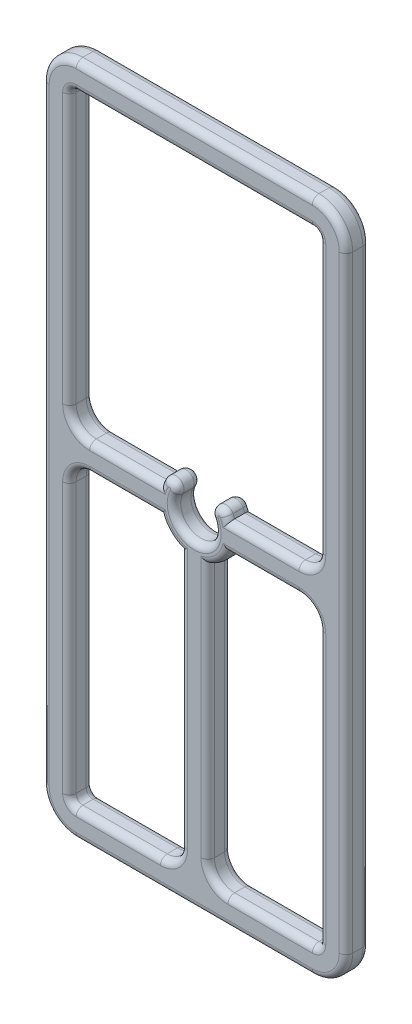
SolidWorks part; units mm, degrees
ref_plane "Front" through (0, 0, 0) normal (0, 0, 1) x (1, 0, 0)
ref_plane "Top" through (0, 0, 0) normal (0, 1, 0) x (1, 0, 0)
ref_plane "Right" through (0, 0, 0) normal (1, 0, 0) x (0, 0, -1)
sketch "Sketch1" plane through (0, 0, 0) normal (0, 0, 1) x (1, 0, 0)
  line L0 (0, -50) -> (0, 50) construction
  line L1 (-18.5, -46) -> (-18.5, -2)
  line L2 (18.5, 46) -> (-18.5, 46)
  line L3 (18.5, -46) -> (18.5, -2)
  line L4 (18.5, -46) -> (2, -46)
  line L5 (-2, -5.016) -> (-2, -46)
  line L6 (2, -5.016) -> (2, -46)
  line L7 (-2, -46) -> (-18.5, -46)
  line L8 (18.5, -46) -> (-18.5, -46) construction
  line L9 (22.5, -50) -> (-22.5, -50)
  line L10 (22.5, -50) -> (22.5, 50)
  line L11 (22.5, 50) -> (-22.5, 50)
  line L12 (-22.5, -50) -> (-22.5, 50)
  line L13 (22.5, -50) -> (-22.5, 50) construction
  line L14 (22.5, 50) -> (-22.5, -50) construction
  line L15 (0, 0) -> (-22.5, 0) construction
  line L16 (-18.5, 2) -> (-5.016, 2)
  line L17 (-18.5, -2) -> (-5.016, -2)
  line L18 (18.5, -2) -> (5.016, -2)
  line L19 (18.5, 2) -> (5.016, 2)
  line L20 (-18.5, 2) -> (-18.5, 46)
  line L21 (-18.5, -46) -> (-18.5, 46) construction
  line L22 (18.5, 2) -> (18.5, 46)
  line L23 (18.5, -46) -> (18.5, 46) construction
  arc A0 (-2.6429, 1.4196) -> (2.6429, 1.4196) centre (0, 0) ccw
  arc A1 (-5.016, -2) -> (-2, -5.016) centre (0, 0) ccw
  arc A2 (-4.7571, 2.5553) -> (-2.6429, 1.4196) centre (-3.7, 1.9875) cw
  arc A3 (4.7571, 2.5553) -> (2.6429, 1.4196) centre (3.7, 1.9875) ccw
  arc A4 (-4.7571, 2.5553) -> (-5.016, 2) centre (0, 0) ccw
  arc A5 (2, -5.016) -> (5.016, -2) centre (0, 0) ccw
  arc A6 (5.016, 2) -> (4.7571, 2.5553) centre (0, 0) ccw
  point P24 (0, 0)
  point P27 (0, 0)
  dimension "D1" = 6
  dimension "D2" = 2.4
  dimension "D3" = 5
  dimension "D4" = 100
  dimension "D5" = 45
  dimension "D7" = 4
  dimension "D8" = 4
  dimension "D6" = 4
extrude "Boss-Extrude2" add sketch "Sketch1" along normal blind 3.5
fillet "Fillet2" radius 5 4 edges at (-22.5, 50, 1.75) (-22.5, -50, 1.75) (22.5, -50, 1.75) (22.5, 50, 1.75)
fillet "Fillet3" radius 1 4 edges at (-18.5, 46, 1.75) (18.5, 46, 1.75) (18.5, -46, 1.75) (-18.5, -46, 1.75)
fillet "Fillet4" radius 3 6 edges at (18.5, 2, 1.75) (-18.5, 2, 1.75) (-18.5, -2, 1.75) (18.5, -2, 1.75) (2, -46, 1.75) (-2, -46, 1.75)
fillet "Fillet5" radius 1 76 edges at (3.8184, -3.8184, 0) (10.258, -2, 0) (17.6213, -2.8787, 0) (18.5, -25, 0) (18.2071, -45.7071, 0) (11.25, -46, 0) (2.8787, -45.1213, 0) (2, -24.008, 0) (-10.258, 2, 0) (-17.6213, 2.8787, 0) (-18.5, 25, 0) (-18.2071, 45.7071, 0) (0, 46, 0) (18.2071, 45.7071, 0) (18.5, 25, 0) (17.6213, 2.8787, 0) (10.258, 2, 0) (4.8944, 2.2813, 0) (3.1322, 3.0446, 0) (0, -3, 0) (-3.1322, 3.0446, 0) (-4.8944, 2.2813, 0) (21.0355, -48.5355, 0) (22.5, 0, 0) (21.0355, 48.5355, 0) (0, 50, 0) (-21.0355, 48.5355, 0) (-22.5, 0, 0) (-21.0355, -48.5355, 0) (0, -50, 0) (-3.8184, -3.8184, 0) (-2, -24.008, 0) (-2.8787, -45.1213, 0) (-11.25, -46, 0) (-18.2071, -45.7071, 0) (-18.5, -25, 0) (-17.6213, -2.8787, 0) (-10.258, -2, 0) (17.6213, -2.8787, 3.5) (10.258, -2, 3.5) (3.8184, -3.8184, 3.5) (2, -24.008, 3.5) (2.8787, -45.1213, 3.5) (11.25, -46, 3.5) (18.2071, -45.7071, 3.5) (18.5, -25, 3.5) (-3.8184, -3.8184, 3.5) (-10.258, -2, 3.5) (-17.6213, -2.8787, 3.5) (-18.5, -25, 3.5) (-18.2071, -45.7071, 3.5) (-11.25, -46, 3.5) (-2.8787, -45.1213, 3.5) (-2, -24.008, 3.5) (0, -3, 3.5) (3.1322, 3.0446, 3.5) (4.8944, 2.2813, 3.5) (10.258, 2, 3.5) (17.6213, 2.8787, 3.5) (18.5, 25, 3.5) (18.2071, 45.7071, 3.5) (0, 46, 3.5) (-18.2071, 45.7071, 3.5) (-18.5, 25, 3.5) (-17.6213, 2.8787, 3.5) (-10.258, 2, 3.5) (-4.8944, 2.2813, 3.5) (-3.1322, 3.0446, 3.5) (-21.0355, 48.5355, 3.5) (0, 50, 3.5) (21.0355, 48.5355, 3.5) (22.5, 0, 3.5) (21.0355, -48.5355, 3.5) (0, -50, 3.5) (-21.0355, -48.5355, 3.5) (-22.5, 0, 3.5)
